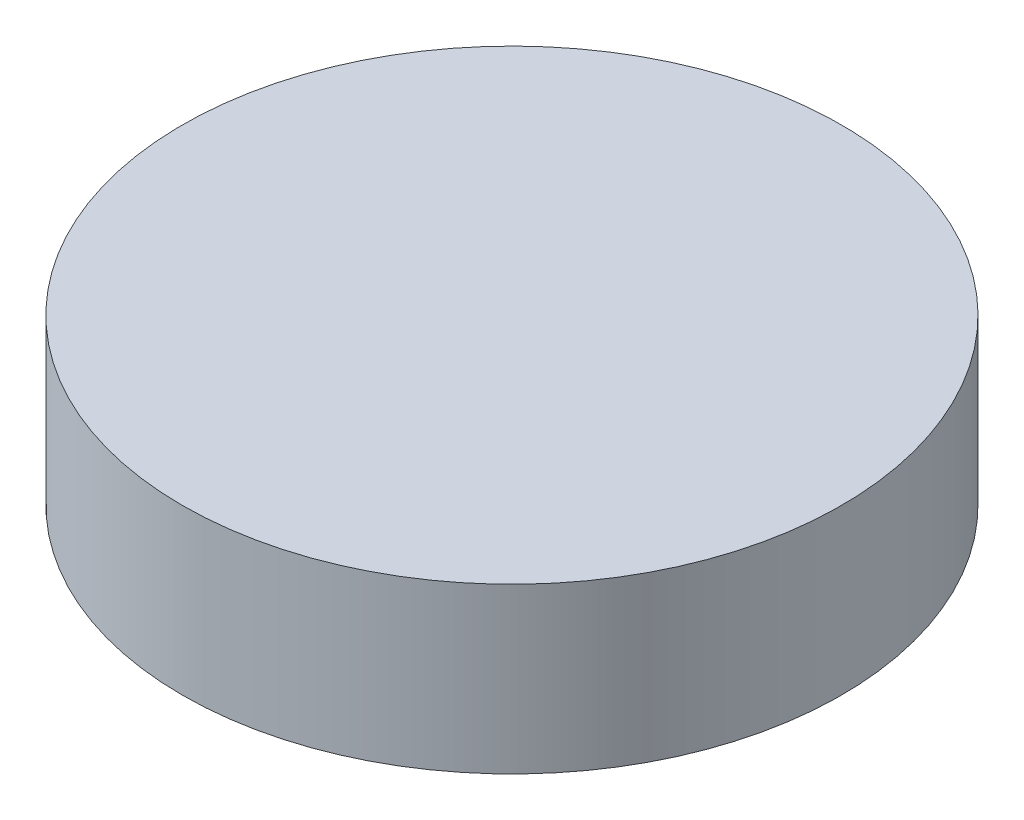
SolidWorks part; units mm, degrees
ref_plane "Front Plane" through (0, 0, 0) normal (0, 0, 1) x (1, 0, 0)
ref_plane "Top Plane" through (0, 0, 0) normal (0, 1, 0) x (1, 0, 0)
ref_plane "Right Plane" through (0, 0, 0) normal (1, 0, 0) x (0, 0, -1)
sketch "Sketch1" plane through (0, 0, 0) normal (0, 1, 0) x (1, 0, 0)
  circle A0 centre (-28.44, -17.5079) radius 12.7359
  dimension "D1" = 25.4718
extrude "Boss-Extrude1" add sketch "Sketch1" along normal blind 6.35
